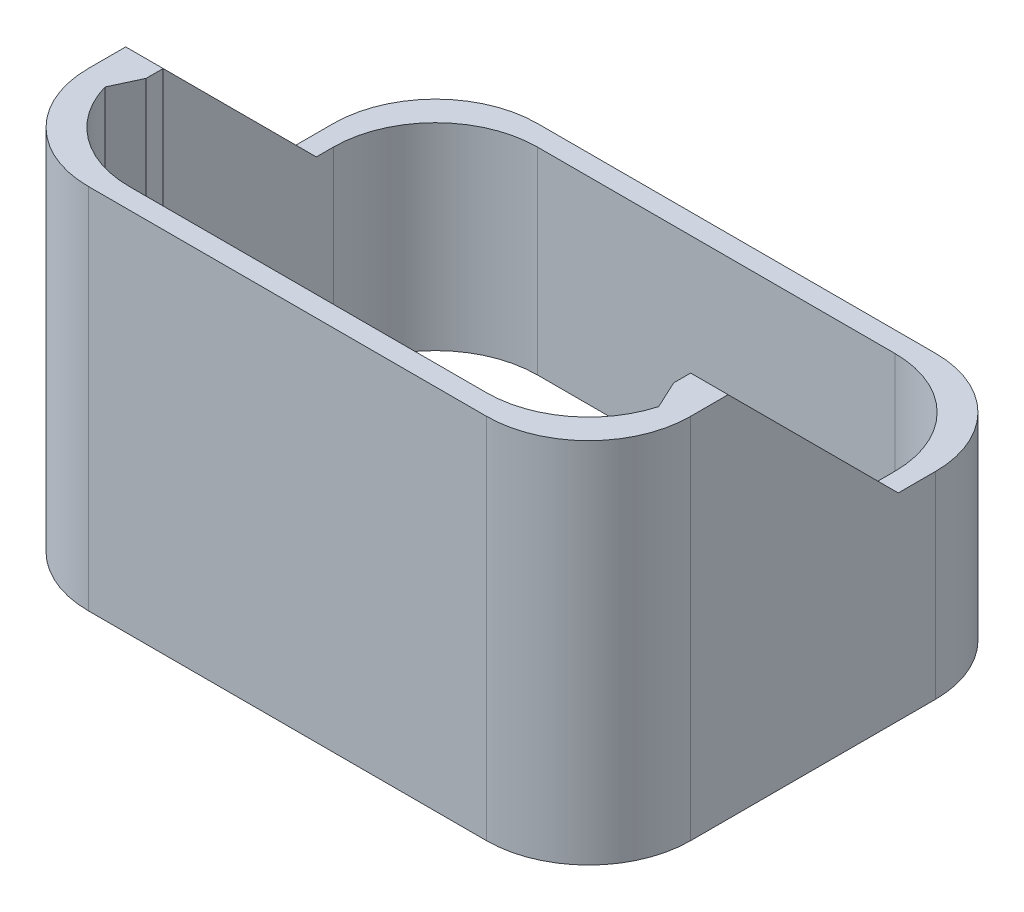
SolidWorks part; units mm, degrees
ref_plane "Front" through (0, 0, 0) normal (0, 0, 1) x (1, 0, 0)
ref_plane "Top" through (0, 0, 0) normal (0, 1, 0) x (1, 0, 0)
ref_plane "Right" through (0, 0, 0) normal (1, 0, 0) x (0, 0, -1)
sketch "Sketch1" plane through (0, 0, 0) normal (0, 1, 0) x (1, 0, 0)
  line L0 (6, 0) -> (29.4, 0)
  line L1 (0, 6) -> (0, 20.4)
  line L2 (6, 26.4) -> (29.4, 26.4)
  line L3 (35.4, 6) -> (35.4, 20.4)
  arc A0 (6, 0) -> (0, 6) centre (6, 6) cw
  arc A1 (29.4, 0) -> (35.4, 6) centre (29.4, 6) ccw
  arc A2 (29.4, 26.4) -> (35.4, 20.4) centre (29.4, 20.4) cw
  arc A3 (0, 20.4) -> (6, 26.4) centre (6, 20.4) cw
  dimension "D1" = 6
  dimension "D2" = 26.4
  dimension "D3" = 35.4
extrude "Boss-Extrude1" add sketch "Sketch1" along normal blind 11.6
sketch "Sketch2" plane through (0, 11.6, 0) normal (0, 1, 0) x (1, 0, 0)
  line L0 (0, 20.4) -> (0, 6) construction
  line L1 (0, 8.2) -> (35.4, 8.2)
  line L2 (0, 8.2) -> (0, 6)
  line L3 (6, 0) -> (29.4, 0)
  line L4 (35.4, 8.2) -> (35.4, 6)
  line L5 (29.4, 26.4) -> (6, 26.4) construction
  arc A0 (0, 6) -> (6, 0) centre (6, 6) ccw
  arc A1 (29.4, 0) -> (35.4, 6) centre (29.4, 6) ccw
  point P12 (35.4, 0)
  dimension "D3" = 6
  dimension "D1" = 18.2
  dimension "D2" = 8.2
extrude "Boss-Extrude2" add sketch "Sketch2" along normal blind 10
chamfer "Chamfer1" distance 10 angle 45 1 edges
sketch "Sketch3" plane through (0, 0, 0) normal (0, -1, 0) x (1, 0, 0)
  line L0 (6, 0) -> (29.4, 0) construction
  line L1 (7.2, -1.2) -> (28.2, -1.2)
  line L2 (1.2, -7.2) -> (1.2, -19.2)
  line L3 (7.2, -25.2) -> (28.2, -25.2)
  line L4 (34.2, -7.2) -> (34.2, -19.2)
  line L5 (35.4, -6) -> (35.4, -20.4) construction
  line L6 (29.4, -26.4) -> (6, -26.4) construction
  line L7 (0, -20.4) -> (0, -6) construction
  arc A0 (28.2, -1.2) -> (34.2, -7.2) centre (28.2, -7.2) cw
  arc A1 (28.2, -25.2) -> (34.2, -19.2) centre (28.2, -19.2) ccw
  arc A2 (1.2, -19.2) -> (7.2, -25.2) centre (7.2, -19.2) ccw
  arc A3 (7.2, -1.2) -> (1.2, -7.2) centre (7.2, -7.2) ccw
  dimension "D5" = 6
  dimension "D1" = 1.2
  dimension "D2" = 1.2
  dimension "D3" = 1.2
  dimension "D4" = 1.2
extrude "Cut-Extrude1" cut sketch "Sketch3" against normal up to next
sketch "Sketch4" plane through (1.2, 0, 0) normal (1, 0, 0) x (0, 0, -1)
  line L0 (7.2, 0) -> (19.2, 0) construction
  line L1 (7.2, 0) -> (8.2, 0)
  line L2 (7.2, 0) -> (7.2, 21.6)
  line L3 (7.2, 21.6) -> (8.2, 21.6)
  line L4 (8.2, 0) -> (8.2, 21.6)
  line L5 (25.2, 11.6) -> (25.2, 0) construction
  dimension "D1" = 1
  dimension "D2" = 17
extrude "Boss-Extrude3" add sketch "Sketch4" along normal blind 1
sketch "Sketch5" plane through (34.2, 0, 0) normal (-1, 0, 0) x (0, 0, 1)
  line L0 (-19.2, 0) -> (-7.2, 0) construction
  line L1 (-8.2, 0) -> (-7.2, 0)
  line L2 (-8.2, 0) -> (-8.2, 21.6)
  line L3 (-8.2, 21.6) -> (-7.2, 21.6)
  line L4 (-7.2, 0) -> (-7.2, 21.6)
  line L5 (-8.2, 21.6) -> (-7.2, 21.6) construction
  line L6 (-25.2, 11.6) -> (-25.2, 0) construction
  dimension "D1" = 1
  dimension "D2" = 17
extrude "Boss-Extrude4" add sketch "Sketch5" along normal blind 1
chamfer "Chamfer2" distance 1 angle 65 2 edges at (34.2, 10.8, -7.2) (1.2, 10.8, -7.2) first distance on face at (33.7, 10.8, -7.2) first distance on face at (1.7, 10.8, -7.2)
